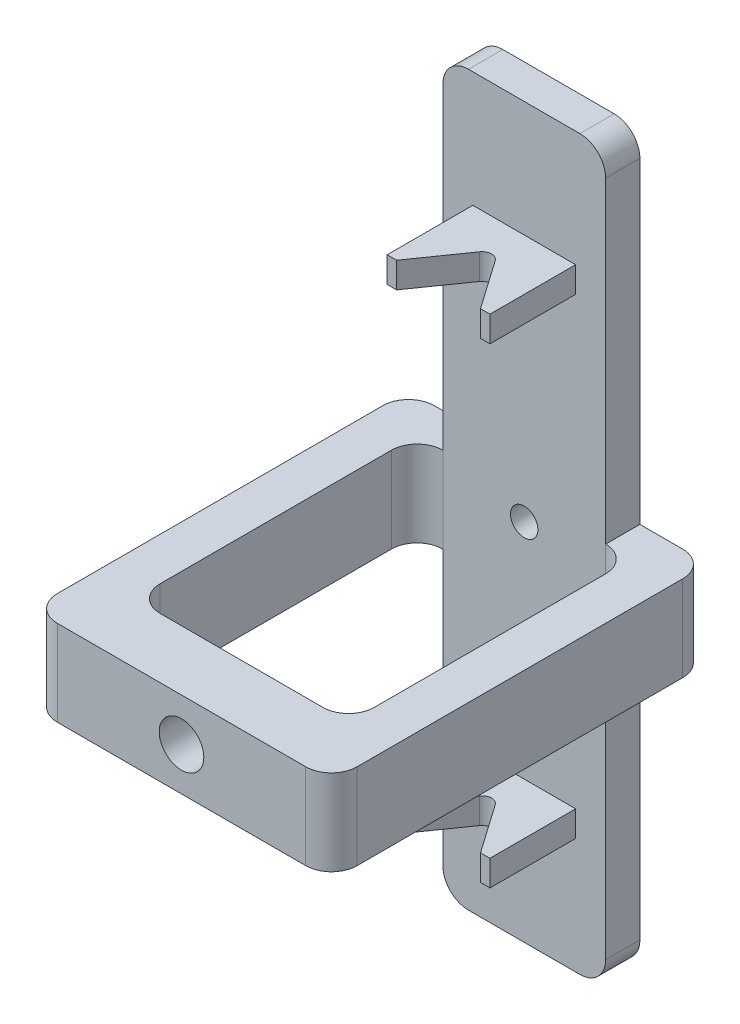
SolidWorks part; units mm, degrees
ref_plane "Front Plane" through (0, 0, 0) normal (0, 0, 1) x (1, 0, 0)
ref_plane "Top Plane" through (0, 0, 0) normal (0, 1, 0) x (1, 0, 0)
ref_plane "Right Plane" through (0, 0, 0) normal (1, 0, 0) x (0, 0, -1)
sketch "Sketch1" plane through (0, 0, 0) normal (0, 0, 1) x (1, 0, 0)
  line L1 (-7.5, 42.5) -> (7.5, 42.5)
  line L2 (-7.5, 42.5) -> (-7.5, -42.5)
  line L3 (-7.5, -42.5) -> (7.5, -42.5)
  line L4 (7.5, 42.5) -> (7.5, -42.5)
  line L5 (-7.5, 42.5) -> (7.5, -42.5) construction
  line L6 (-7.5, -42.5) -> (7.5, 42.5) construction
  point P0 (0, 0)
  dimension "D1" = 85
  dimension "D2" = 15
extrude "Boss-Extrude1" add sketch "Sketch1" along normal blind 4
sketch "Sketch2" plane through (0, 0, 4) normal (0, 0, 1) x (1, 0, 0)
  line L0 (0, 42.5) -> (0, 27.5)
  line L1 (0, -42.5) -> (0, -27.5)
  line L3 (-6, 29) -> (6, 29)
  line L4 (7.5, -42.5) -> (7.5, 42.5)
  line L5 (7.5, 42.5) -> (-7.5, 42.5)
  line L6 (-7.5, 42.5) -> (-7.5, -42.5)
  line L7 (-7.5, -42.5) -> (7.5, -42.5)
  line L9 (7.5, 42.5) -> (-7.5, 42.5)
  line L11 (-7.5, -42.5) -> (7.5, -42.5)
  line L12 (-6, 29) -> (-6, 26)
  line L13 (-6, 26) -> (6, 26)
  line L14 (6, 29) -> (6, 26)
  line L15 (-6, 29) -> (6, 26) construction
  line L16 (-6, 26) -> (6, 29) construction
  line L17 (-6, -29) -> (6, -29)
  line L18 (-6, -29) -> (-6, -26)
  line L19 (-6, -26) -> (6, -26)
  line L20 (6, -29) -> (6, -26)
  line L21 (-6, -29) -> (6, -26) construction
  line L22 (-6, -26) -> (6, -29) construction
  dimension "D2" = 15
  dimension "D3" = 15
  dimension "D4" = 3
  dimension "D5" = 12
  dimension "D6" = 3
  dimension "D7" = 12
  dimension "D1" = 0
extrude "Boss-Extrude2" add sketch "Sketch2" along normal blind 10 contours L14 L3 L12 L13 | L17 L20 L19 L18 region at (3, 28.8763, 4) region at (-3, -28.8763, 4)
sketch "Sketch3" plane through (0, 29, 0) normal (0, 1, 0) x (1, 0, 0)
  line L0 (0, -14) -> (0, -7)
  line L1 (-0.9046, -8.2934) -> (-4.896, -14)
  line L2 (0.9046, -8.2934) -> (4.896, -14)
  line L4 (6, -4) -> (-6, -4)
  line L5 (-6, -4) -> (-6, -14)
  line L6 (-6, -14) -> (6, -14)
  line L7 (6, -14) -> (6, -4)
  line L8 (6, -4) -> (-6, -4)
  line L9 (-6, -4) -> (-6, -12.896)
  line L10 (-4.896, -14) -> (4.896, -14)
  line L11 (6, -12.896) -> (6, -4)
  arc A0 (6, -12.896) -> (4.896, -14) centre (4.896, -12.896) cw
  arc A1 (-4.896, -14) -> (-6, -12.896) centre (-4.896, -12.896) cw
  arc A2 (0.9046, -8.2934) -> (-0.9046, -8.2934) centre (0, -8.9261) ccw
  line M9 (-6, -14) -> (6, -14)
  dimension "D2" = 1.104
  dimension "D4" = 1.104
  dimension "D3" = 7
  dimension "D1" = 0
extrude "Cut-Extrude1" cut sketch "Sketch3" against normal blind 60 contours L2 A2 L0 M9 | L0 A2 L1 M9 region at (-1.6555, 29, 11.7355) region at (1.6555, 29, 11.7355)
sketch "Sketch4" plane through (0, 0, 4) normal (0, 0, 1) x (1, 0, 0)
  line L0 (0, 0) -> (0, -15.4)
  circle A0 centre (0, -15.4) radius 1.6
  circle A1 centre (0, 0) radius 1.6
  dimension "D2" = 3.2
  dimension "D3" = 3.2
  dimension "D1" = 15.4
extrude "Cut-Extrude2" cut sketch "Sketch4" against normal blind 4 contours A1 | A0 region at (1.0994, -14.3006, 4) region at (-1.0994, 1.0994, 4)
sketch "Sketch5" plane through (0, 42.5, 0) normal (0, 1, 0) x (1, 0, 0)
  line L1 (7.5, 0) -> (17.5, 0)
  line L2 (7.5, 0) -> (7.5, -4)
  line L3 (7.5, -4) -> (17.5, -4)
  line L4 (17.5, 0) -> (17.5, -4)
  line L5 (-7.5, 0) -> (-17.5, 0)
  line L6 (-7.5, 0) -> (-7.5, -4)
  line L7 (-7.5, -4) -> (-17.5, -4)
  line L8 (-17.5, 0) -> (-17.5, -4)
  dimension "D1" = 10
  dimension "D2" = 10
  dimension "D3" = 4
  dimension "D4" = 4
extrude "Boss-Extrude3" add sketch "Sketch5" against normal blind 50
sketch "Sketch8" plane through (0, 0, 4) normal (0, 0, 1) x (1, 0, 0)
  line L1 (17.5, 42.5) -> (7.5, 42.5)
  line L2 (17.5, 42.5) -> (17.5, 2.5)
  line L3 (17.5, 2.5) -> (7.5, 2.5)
  line L4 (7.5, 42.5) -> (7.5, 2.5)
  line L5 (-17.5, 42.5) -> (-7.5, 42.5)
  line L6 (-17.5, 42.5) -> (-17.5, 2.5)
  line L7 (-17.5, 2.5) -> (-7.5, 2.5)
  line L8 (-7.5, 42.5) -> (-7.5, 2.5)
  dimension "D1" = 40
  dimension "D2" = 10
  dimension "D3" = 40
  dimension "D4" = 10
extrude "Cut-Extrude3" cut sketch "Sketch8" against normal blind 4
sketch "Sketch10" plane through (0, 0, 4) normal (0, 0, 1) x (1, 0, 0)
  line L1 (17.5, 2.5) -> (7.5, 2.5)
  line L2 (17.5, 2.5) -> (17.5, -7.5)
  line L3 (17.5, -7.5) -> (7.5, -7.5)
  line L4 (7.5, 2.5) -> (7.5, -7.5)
  line L5 (-17.5, 2.5) -> (-7.5, 2.5)
  line L6 (-17.5, 2.5) -> (-17.5, -7.5)
  line L7 (-17.5, -7.5) -> (-7.5, -7.5)
  line L8 (-7.5, 2.5) -> (-7.5, -7.5)
extrude "Boss-Extrude4" add sketch "Sketch10" along normal blind 40
sketch "Sketch11" plane through (7.5, 0, 0) normal (-1, 0, 0) x (0, 0, 1)
  line L1 (44, 2.5) -> (37, 2.5)
  line L2 (44, 2.5) -> (44, -7.5)
  line L3 (44, -7.5) -> (37, -7.5)
  line L4 (37, 2.5) -> (37, -7.5)
  dimension "D1" = 10
  dimension "D2" = 7
extrude "Boss-Extrude5" add sketch "Sketch11" along normal up to surface (15 mm away) up to face at (-7.5, -2.5, 24)
sketch "Sketch13" plane through (0, 2.5, 0) normal (0, 1, 0) x (1, 0, 0)
  line L3 (-7.5, -4) -> (-12.5, -4)
  line L4 (-7.5, -4) -> (-7.5, -37)
  line L5 (-7.5, -37) -> (-12.5, -37)
  line L6 (-12.5, -4) -> (-12.5, -37)
  line L7 (7.5, -4) -> (12.5, -4)
  line L8 (7.5, -4) -> (7.5, -37)
  line L9 (7.5, -37) -> (12.5, -37)
  line L10 (12.5, -4) -> (12.5, -37)
  dimension "D1" = 33
  dimension "D2" = 5
  dimension "D3" = 33
  dimension "D4" = 5
extrude "Cut-Extrude4" cut sketch "Sketch13" against normal blind 10
sketch "Sketch14" plane through (0, 0, 44) normal (0, 0, 1) x (1, 0, 0)
  line L0 (0, -7.5) -> (0, 2.5)
  line L1 (-17.5, -7.5) -> (17.5, -7.5) construction
  line L2 (17.5, 2.5) -> (-17.5, 2.5) construction
  circle A0 centre (0, -2.5) radius 2.6
  dimension "D1" = 5.2
extrude "Cut-Extrude6" cut sketch "Sketch14" against normal up to surface (7 mm away) contours L0 A0 | L0 A0 region at (-1.1035, -2.5, 44) region at (1.1035, -2.5, 44) up to face at (0, -2.5, 37)
sketch "Sketch17" plane through (7.5, 0, 0) normal (1, 0, 0) x (0, 0, -1)
  line L4 (0, -42.5) -> (0, -7.5)
  line L5 (0, -7.5) -> (-4, -7.5)
  line L6 (-4, -7.5) -> (-4, -42.5)
  line L7 (-4, -42.5) -> (0, -42.5)
  line L8 (0, -42.5) -> (0, -7.5)
  line L9 (0, -7.5) -> (-4, -7.5)
  line L10 (-4, -7.5) -> (-4, -42.5)
  line L11 (-4, -42.5) -> (0, -42.5)
  line L12 (-4, 42.5) -> (-4, 2.5)
  line L13 (-4, 2.5) -> (0, 2.5)
  line L14 (0, 2.5) -> (0, 42.5)
  line L15 (0, 42.5) -> (-4, 42.5)
  line L16 (-4, 42.5) -> (-4, 2.5)
  line L17 (-4, 2.5) -> (0, 2.5)
  line L18 (0, 2.5) -> (0, 42.5)
  line L19 (0, 42.5) -> (-4, 42.5)
  dimension "D1" = 0
  dimension "D2" = 0
extrude "Boss-Extrude6" add sketch "Sketch17" along normal blind 2
sketch "Sketch18" plane through (-7.5, 0, 0) normal (-1, 0, 0) x (0, 0, 1)
  line L4 (4, -42.5) -> (4, -7.5)
  line L5 (4, -7.5) -> (0, -7.5)
  line L6 (0, -7.5) -> (0, -42.5)
  line L7 (0, -42.5) -> (4, -42.5)
  line L8 (4, -42.5) -> (4, -7.5)
  line L9 (4, -7.5) -> (0, -7.5)
  line L10 (0, -7.5) -> (0, -42.5)
  line L11 (0, -42.5) -> (4, -42.5)
  line L12 (4, 2.5) -> (4, 42.5)
  line L13 (4, 42.5) -> (0, 42.5)
  line L14 (0, 42.5) -> (0, 2.5)
  line L15 (0, 2.5) -> (4, 2.5)
  line L16 (4, 2.5) -> (4, 42.5)
  line L17 (4, 42.5) -> (0, 42.5)
  line L18 (0, 42.5) -> (0, 2.5)
  line L19 (0, 2.5) -> (4, 2.5)
  dimension "D1" = 0
  dimension "D2" = 0
extrude "Boss-Extrude7" add sketch "Sketch18" along normal blind 2
fillet "Fillet2" radius 3 12 edges at (9.5, -42.5, 2) (-9.5, -42.5, 2) (9.5, 42.5, 2) (-9.5, 42.5, 2) (-17.5, -2.5, 0) (17.5, -2.5, 44) (-17.5, -2.5, 44) (12.5, -2.5, 37) (-12.5, -2.5, 37) (17.5, -2.5, 0) (12.5, -2.5, 4) (-12.5, -2.5, 4)
